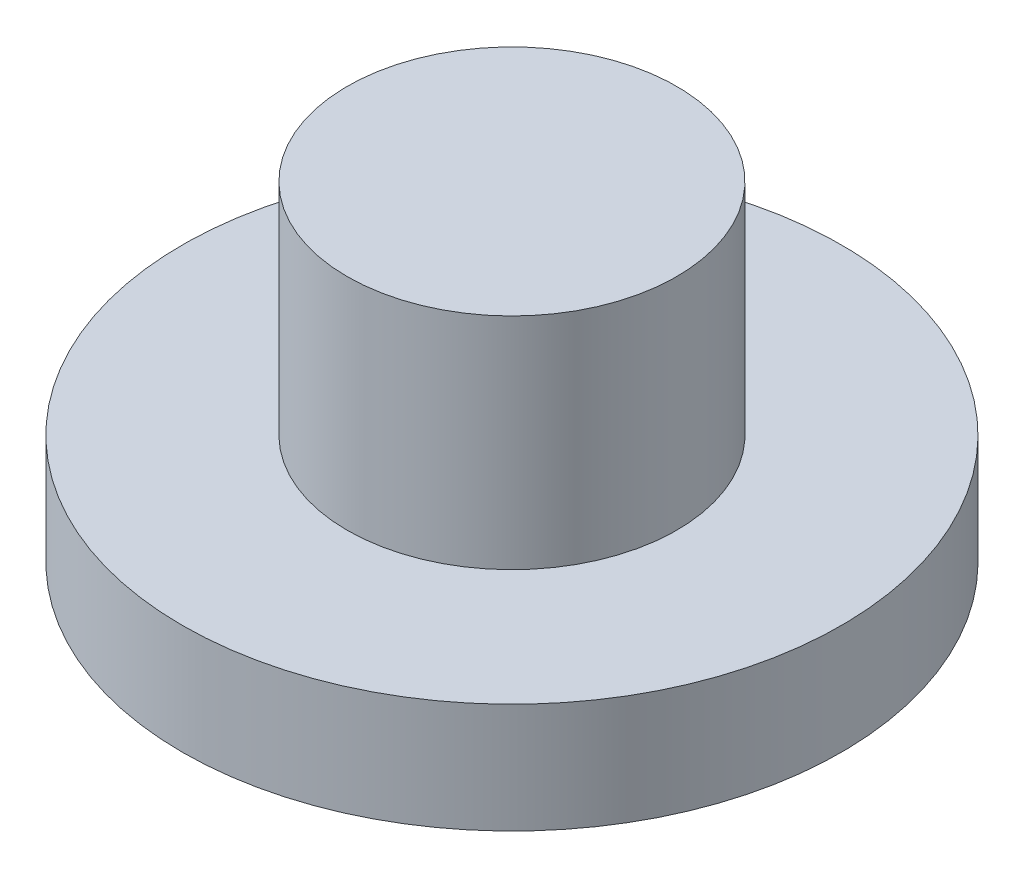
SolidWorks part; units mm, degrees
ref_plane "Спереди" through (0, 0, 0) normal (0, 0, 1) x (1, 0, 0)
ref_plane "Сверху" through (0, 0, 0) normal (0, 1, 0) x (1, 0, 0)
ref_plane "Справа" through (0, 0, 0) normal (1, 0, 0) x (0, 0, -1)
sketch "Эскиз1" plane through (0, 0, 0) normal (0, 1, 0) x (1, 0, 0)
  circle A0 centre (0, 0) radius 30
  dimension "D1" = 60
extrude "Бобышка-Вытянуть1" add sketch "Эскиз1" along normal blind 10
sketch "Эскиз2" plane through (0, 10, 0) normal (0, 1, 0) x (1, 0, 0)
  circle A0 centre (0, 0) radius 15
  dimension "D1" = 30
extrude "Бобышка-Вытянуть2" add sketch "Эскиз2" along normal blind 20
